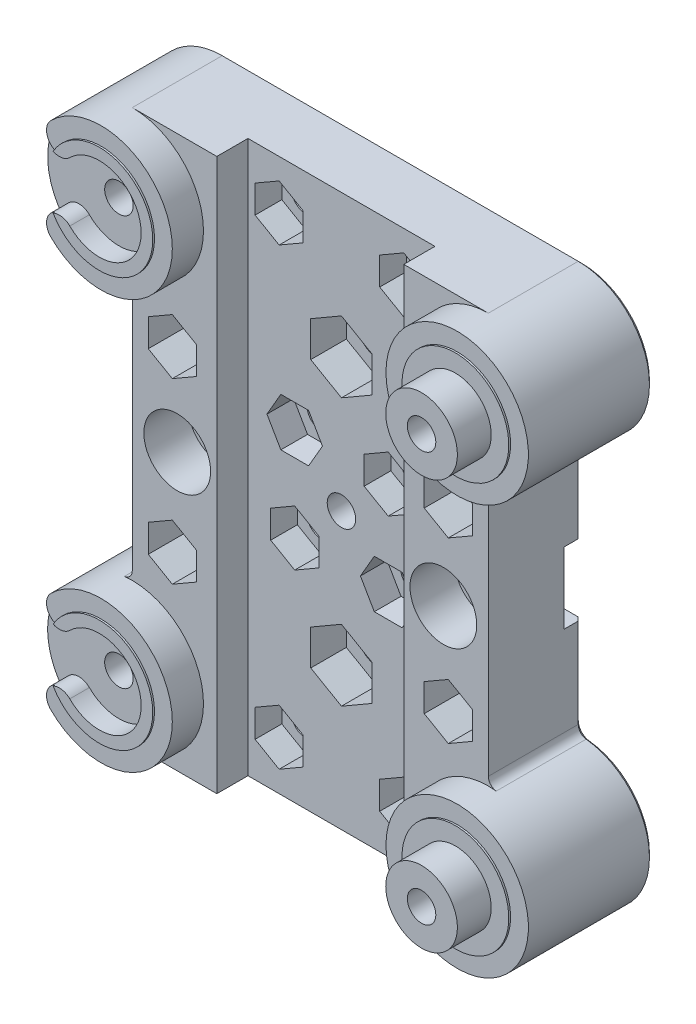
SolidWorks part; units mm, degrees
note: The reader was unsure of these and kept them because the rebuilt part matched: shared geometry of "草图31<3>".
ref_plane "前视基准面" through (0, 0, 0) normal (0, 0, 1) x (1, 0, 0)
ref_plane "上视基准面" through (0, 0, 0) normal (0, 1, 0) x (1, 0, 0)
ref_plane "右视基准面" through (0, 0, 0) normal (1, 0, 0) x (0, 0, -1)
sketch "草图2" plane through (0, 0, 0) normal (0, 0, 1) x (1, 0, 0)
  line L1 (-20, -31) -> (20, -31)
  line L2 (-20, -31) -> (-20, 31)
  line L3 (-20, 31) -> (20, 31)
  line L4 (20, -31) -> (20, 31)
  line L5 (-20, -31) -> (20, 31) construction
  line L6 (-20, 31) -> (20, -31) construction
  point P0 (0, 0)
  dimension "D1" = 40
  dimension "D2" = 62
extrude "凸台-拉伸1" add sketch "草图2" along normal blind 10.5
sketch "草图3" plane through (0, 0, 0) normal (0, 0, -1) x (-1, 0, 0)
  line L2 (20, 31) -> (20, 15)
  arc A0 (20, 15) -> (20, 31) centre (20, 23) ccw
  dimension "D1" = 20
  dimension "D2" = 23
extrude "凸台-拉伸2" add sketch "草图3" against normal blind 10.5
sketch "草图5" plane through (0, 0, 0) normal (0, 0, -1) x (-1, 0, 0)
  line L1 (21.6166, 25.8) -> (18.3834, 25.8)
  line L2 (18.3834, 25.8) -> (16.7668, 23)
  line L3 (16.7668, 23) -> (18.3834, 20.2)
  line L4 (18.3834, 20.2) -> (21.6166, 20.2)
  line L5 (21.6166, 20.2) -> (23.2332, 23)
  line L6 (23.2332, 23) -> (21.6166, 25.8)
  circle A1 centre (20, 23) radius 2.8 construction
  dimension "D1" = 5.6
extrude "切除-拉伸1" cut sketch "草图5" against normal blind 5
sketch "草图29" plane through (0, 0, 10.5) normal (0, 0, 1) x (1, 0, 0)
  circle A0 centre (-20, 23) radius 8
extrude "凸台-拉伸5" add sketch "草图29" along normal blind 3.5
sketch "草图7" plane through (0, 0, 14) normal (0, 0, 1) x (1, 0, 0)
  circle A0 centre (-20, 23) radius 4.025
  dimension "D1" = 8.05
extrude "凸台-拉伸3" add sketch "草图7" along normal blind 9
sketch "草图8" plane through (0, 0, 23) normal (0, 0, 1) x (1, 0, 0)
  circle A0 centre (-20, 23) radius 1.6
  dimension "D1" = 3.2
extrude "切除-拉伸2" cut sketch "草图8" against normal through all
sketch "草图12" plane through (0, 0, 14) normal (0, 0, 1) x (1, 0, 0)
  circle A0 centre (-20, 23) radius 4.025 construction
  circle A1 centre (-20, 23) radius 4.025
  circle A2 centre (-20, 23) radius 6
  dimension "D1" = 12
extrude "凸台-拉伸4" add sketch "草图12" along normal blind 0.2
sketch "草图13" plane through (0, 0, 0) normal (0, 0, -1) x (-1, 0, 0)
  circle A0 centre (-15.5, -10) radius 1.6
  dimension "D1" = 3.2
  dimension "D2" = 10
  dimension "D3" = 15.5
extrude "切除-拉伸5" cut sketch "草图13" against normal through all both and the other way through all
mirror "镜向3" about plane through (0, 0, 0) normal (0, 1, 0) of "切除-拉伸5"
mirror "镜向4" about plane through (0, 0, 0) normal (1, 0, 0) of "切除-拉伸5", "镜向3"
sketch "草图14" plane through (0, 0, 0) normal (0, 0, -1) x (-1, 0, 0)
  line L0 (20, 15) -> (20, -31) construction
  circle A0 centre (14.95, 0) radius 2.05
  dimension "D1" = 4.1
  dimension "D2" = 5.05
extrude "切除-拉伸6" cut sketch "草图14" against normal through all both and the other way through all
sketch "草图15" plane through (0, 0, 0) normal (0, 0, -1) x (-1, 0, 0)
  line L1 (-5.25, -5.25) -> (5.25, -5.25) construction
  line L2 (-5.25, -5.25) -> (-5.25, 5.25) construction
  line L3 (-5.25, 5.25) -> (5.25, 5.25) construction
  line L4 (5.25, -5.25) -> (5.25, 5.25) construction
  line L5 (-5.25, -5.25) -> (5.25, 5.25) construction
  line L6 (-5.25, 5.25) -> (5.25, -5.25) construction
  circle A0 centre (5.25, 5.25) radius 1.6
  point P0 (0, 0)
  dimension "D3" = 3.2
  dimension "D1" = 10.5
  dimension "D2" = 10.5
extrude "切除-拉伸7" cut sketch "草图15" against normal through all both and the other way through all
sketch "草图16" plane through (0, 0, 0) normal (0, 0, -1) x (-1, 0, 0)
  circle A0 centre (0, 0) radius 1.6
  dimension "D1" = 3.2
extrude "切除-拉伸8" cut sketch "草图16" against normal through all both and the other way through all
pattern_circular "阵列(圆周)1" count 4 over 360 about axis through (0, 0, 0) along (0, 0, 1) of "切除-拉伸7"
mirror "镜向5" about plane through (0, 0, 0) normal (1, 0, 0) of "切除-拉伸6"
sketch "草图17" plane through (0, 0, 10.5) normal (0, 0, 1) x (1, 0, 0)
  line L1 (-12.8, 11.5588) -> (-15.5, 13.1177)
  line L2 (-15.5, 13.1177) -> (-18.2, 11.5588)
  line L3 (-18.2, 11.5588) -> (-18.2, 8.4412)
  line L4 (-18.2, 8.4412) -> (-15.5, 6.8823)
  line L5 (-15.5, 6.8823) -> (-12.8, 8.4412)
  line L6 (-12.8, 8.4412) -> (-12.8, 11.5588)
  line L7 (-20, 15) -> (-20, -31) construction
  circle A0 centre (-15.5, 10) radius 2.7 construction
  dimension "D1" = 5.4
extrude "切除-拉伸9" cut sketch "草图17" against normal blind 5 and the other way through all
sketch "草图19" plane through (0, 0, 10.5) normal (0, 0, 1) x (1, 0, 0)
  circle A0 centre (-14.95, 0) radius 3.75
  dimension "D1" = 7.5
extrude "切除-拉伸11" cut sketch "草图19" against normal blind 5
mirror "镜向6" about plane through (0, 0, 0) normal (0, 1, 0) of "凸台-拉伸5", "凸台-拉伸2", "切除-拉伸9", "凸台-拉伸3", "凸台-拉伸4", "切除-拉伸1", "切除-拉伸2"
sketch "草图18" plane through (0, 0, 10.5) normal (0, 0, 1) x (1, 0, 0)
  line L0 (-20, -31) -> (20, -31) construction
  line L1 (-10.5, 31) -> (10.5, 31)
  line L2 (-10.5, 31) -> (-10.5, -31)
  line L3 (-10.5, -31) -> (10.5, -31)
  line L4 (10.5, 31) -> (10.5, -31)
  line L5 (-10.5, 31) -> (10.5, -31) construction
  line L6 (-10.5, -31) -> (10.5, 31) construction
  point P0 (0, 0)
  dimension "D1" = 21
extrude "切除-拉伸10" cut sketch "草图18" against normal offset from surface (3.5 mm away) 7 up to face at (12.9, 0, 0)
mirror "镜向7" about plane through (0, 0, 0) normal (1, 0, 0) of "凸台-拉伸5", "凸台-拉伸3", "切除-拉伸1", "凸台-拉伸2", "切除-拉伸2", "凸台-拉伸4", "切除-拉伸5", "镜向3", "镜向4", "切除-拉伸6", "镜向5", "切除-拉伸9", "切除-拉伸11", "镜向6"
sketch "草图20" plane through (0, 0, 7) normal (0, 0, 1) x (1, 0, 0)
  line L1 (-3.6912, 7.95) -> (-6.8088, 7.95)
  line L2 (-6.8088, 7.95) -> (-8.3677, 5.25)
  line L3 (-8.3677, 5.25) -> (-6.8088, 2.55)
  line L4 (-6.8088, 2.55) -> (-3.6912, 2.55)
  line L5 (-3.6912, 2.55) -> (-2.1323, 5.25)
  line L6 (-2.1323, 5.25) -> (-3.6912, 7.95)
  circle A0 centre (-5.25, 5.25) radius 2.7 construction
  dimension "D1" = 5.4
extrude "切除-拉伸12" cut sketch "草图20" against normal blind 3
pattern_circular "阵列(圆周)2" count 4 over 360 about axis through (0, 0, 0) along (0, 0, 1) of "切除-拉伸12"
sketch "草图21" plane through (0, 0, 7) normal (0, 0, 1) x (1, 0, 0)
  line L0 (10.5, 31) -> (-10.5, 31) construction
  line L1 (-4.3, 27.0588) -> (-7, 28.6177)
  line L2 (-7, 28.6177) -> (-9.7, 27.0588)
  line L3 (-9.7, 27.0588) -> (-9.7, 23.9412)
  line L4 (-9.7, 23.9412) -> (-7, 22.3823)
  line L5 (-7, 22.3823) -> (-4.3, 23.9412)
  line L6 (-4.3, 23.9412) -> (-4.3, 27.0588)
  circle A0 centre (-7, 25.5) radius 2.7 construction
  point P1 (-4.3, 25.5)
  point P9 (-9.7, 25.5)
  dimension "D1" = 5.4
  dimension "D2" = 5.5
  dimension "D3" = 7
extrude "切除-拉伸13" cut sketch "草图21" against normal blind 3
sketch "草图22" plane through (0, 0, 4) normal (0, 0, 1) x (1, 0, 0)
  line L0 (10.5, 31) -> (-10.5, 31) construction
  circle A0 centre (-7, 25.5) radius 1.6
  dimension "D1" = 3.2
  dimension "D2" = 7
  dimension "D3" = 5.5
extrude "切除-拉伸14" cut sketch "草图22" against normal through all
mirror "镜向8" about plane through (0, 0, 0) normal (1, 0, 0) of "切除-拉伸13", "切除-拉伸14"
sketch "草图23" plane through (0, 0, 7) normal (0, 0, 1) x (1, 0, 0)
  line L0 (10.5, 31) -> (-10.5, 31) construction
  circle A0 centre (0, 15) radius 2.1
  dimension "D2" = 4.2
  dimension "D1" = 16
extrude "切除-拉伸15" cut sketch "草图23" against normal through all
sketch "草图24" plane through (0, 0, 7) normal (0, 0, 1) x (1, 0, 0)
  line L1 (0, 18.9837) -> (-3.45, 16.9919)
  line L2 (-3.45, 16.9919) -> (-3.45, 13.0081)
  line L3 (-3.45, 13.0081) -> (0, 11.0163)
  line L4 (0, 11.0163) -> (3.45, 13.0081)
  line L5 (3.45, 13.0081) -> (3.45, 16.9919)
  line L6 (3.45, 16.9919) -> (0, 18.9837)
  circle A0 centre (0, 15) radius 3.45 construction
  dimension "D1" = 6.9
extrude "切除-拉伸16" cut sketch "草图24" against normal blind 4
mirror "镜向9" about plane through (0, 0, 0) normal (0, 1, 0) of "切除-拉伸16", "切除-拉伸15", "镜向8", "切除-拉伸13", "切除-拉伸14"
sketch "草图25" plane through (0, 0, 23) normal (0, 0, 1) x (1, 0, 0)
  circle A1 centre (20, 23) radius 4.025
  circle A2 centre (20, 23) radius 4.025
  circle A3 centre (20, -23) radius 4.025
  circle A4 centre (20, -23) radius 4.025
  dimension "D1" = 0
  dimension "D2" = 0
extrude "切除-拉伸17" cut sketch "草图25" against normal offset from surface (5 mm away) 4 up to face at (26, 23, 14)
sketch "草图26" plane through (0, 0, 23) normal (0, 0, 1) x (1, 0, 0)
  circle A0 centre (-20, 23) radius 4.7
  dimension "D1" = 9.4
extrude "切除-拉伸18" cut sketch "草图26" against normal blind 11
sketch "草图27" plane through (0, 0, 12) normal (0, 0, 1) x (1, 0, 0)
  line L0 (-24.4802, 27.5) -> (-20, 23) construction
  line L1 (-20, 23) -> (-29.8572, 23) construction
  arc A0 (-25.6444, 28.6693) -> (-23.3161, 26.3307) centre (-24.4802, 27.5) ccw
  circle A1 centre (-20, 23) radius 1.6 construction
  arc A2 (-25.6444, 17.3307) -> (-23.3161, 19.6693) centre (-24.4802, 18.5) cw
  arc A4 (-20, 15) -> (-20, 31) centre (-20, 23) ccw construction
  arc A5 (-23.3161, 26.3307) -> (-23.3161, 19.6693) centre (-20, 23) ccw
  arc A6 (-25.6444, 28.6693) -> (-25.6444, 17.3307) centre (-20, 23) ccw
  dimension "D1" = 6.35
  dimension "D2" = 3.3
  dimension "D3" = 4.5
extrude "切除-拉伸19" cut sketch "草图27" along normal through all
mirror "镜向12" about plane through (0, 0, 0) normal (0, 1, 0) of "切除-拉伸19", "切除-拉伸18"
sketch "草图28" plane through (0, 0, 0) normal (0, 1, 0) x (1, 0, 0)
  line L0 (-20, 0) -> (-28, -3)
  line L1 (-20, 0) -> (-28, 0) construction
  line L2 (-28, 0) -> (-28, -12) construction
  line L3 (-28, -3) -> (-28, 0)
  line L4 (-28, 0) -> (-20, 0)
  line L5 (20, 0) -> (-20, 0) construction
  line L6 (-20, -10.5) -> (-20, 0) construction
  dimension "D1" = 3
extrude "切除-拉伸20" [suppressed] cut sketch "草图28" against normal through all both and the other way through all
mirror "镜向13" [suppressed] about plane through (0, 0, 0) normal (1, 0, 0)
fillet "圆角1" radius 1 4 edges at (-20, 15, 5.25) (-20, -15, 5.25) (20, 15, 5.25) (20, -15, 5.25)
sketch "草图31" plane through (0, 0, 5) normal (0, 0, -1) x (-1, 0, 0)
  line L6 (-21.6, 25.8) -> (-21.6, 20.2)
  line L7 (-18.4, 25.8) -> (-18.4, 20.2)
  line L8 (-22.3094, 24.6) -> (-17.6906, 24.6)
  line L9 (-22.3094, 21.4) -> (-17.6906, 21.4)
  line L12 (-21.6166, 25.8) -> (-23.2332, 23)
  line L13 (-23.2332, 23) -> (-21.6166, 20.2)
  line L14 (-21.6166, 20.2) -> (-18.3834, 20.2)
  line L15 (-18.3834, 20.2) -> (-16.7668, 23)
  line L16 (-16.7668, 23) -> (-18.3834, 25.8)
  line L17 (-18.3834, 25.8) -> (-21.6166, 25.8)
  line L18 (-21.6166, 25.8) -> (-23.2332, 23)
  line L19 (-23.2332, 23) -> (-21.6166, 20.2)
  line L20 (-21.6166, 20.2) -> (-18.3834, 20.2)
  line L21 (-18.3834, 20.2) -> (-16.7668, 23)
  line L22 (-16.7668, 23) -> (-18.3834, 25.8)
  line L23 (-18.3834, 25.8) -> (-21.6166, 25.8)
  circle A0 centre (-20, 23) radius 1.6 construction
  line M12 (-21.6166, 25.8) -> (-23.2332, 23)
  line M13 (-23.2332, 23) -> (-21.6166, 20.2)
  line M14 (-21.6166, 20.2) -> (-18.3834, 20.2)
  line M15 (-18.3834, 20.2) -> (-16.7668, 23)
  line M16 (-16.7668, 23) -> (-18.3834, 25.8)
  line M17 (-18.3834, 25.8) -> (-21.6166, 25.8)
  dimension "D1" = 0
extrude "凸台-拉伸6" add sketch "草图31" along normal blind 0.2 contours L6 L8 L7 M17 | L8 L6 M12 M17 | L7 L8 M16 M17 | L9 L7 M14 M15 | L9 L6 L7 M14 | L9 L6 M13 M14
extrude "凸台-拉伸7" add sketch "草图31<3>" along normal blind 0.4 contours L8 L6 M12 M17 | L9 L6 L8 M13 M12 | L9 L6 M13 M14 | L7 L8 M16 M17 | L7 L9 L8 M15 M16 | L9 L7 M14 M15
sketch "草图31<3>" plane through (0, 0, 5) normal (0, 0, -1) x (-1, 0, 0) same geometry as "草图31"
mirror "镜向14" about plane through (0, 0, 0) normal (0, 1, 0) of "凸台-拉伸6", "凸台-拉伸7"
mirror "镜向15" about plane through (0, 0, 0) normal (1, 0, 0) of "镜向14", "凸台-拉伸6", "凸台-拉伸7"
sketch "草图32" plane through (0, 0, 0) normal (0, 1, 0) x (1, 0, 0)
  line L0 (18, 0) -> (20, -2)
  line L1 (20, 0) -> (-20, 0) construction
  line L2 (20, -10.5) -> (20, 0) construction
  line L5 (18, 0) -> (20, 0)
  line L6 (20, 0) -> (20, -2)
  dimension "D1" = 2
  dimension "D2" = 2
extrude "切除-拉伸22" cut sketch "草图32" against normal mid plane 8
mirror "镜向16" about plane through (0, 0, 0) normal (1, 0, 0) of "切除-拉伸22"
chamfer "倒角1" distance 0.4 angle 45 14 edges at (20, 9.0279, 0) (-20, -9.0279, 0) (0, -31, 0) (0, 31, 0) (-27.9876, -23.4451, 0) (-20, 9.0279, 0) (-27.9876, 23.4451, 0) (20, -9.0279, 0) (27.9876, -23.4451, 0) (27.9876, 23.4451, 0) (-20.2546, -14.7224, 0) (-20.2546, 14.7224, 0) (20.2546, -14.7224, 0) (20.2546, 14.7224, 0)
chamfer "倒角2" distance 0.4 angle 45 17 edges at (5.4, 25.5, 0) (-5.4, 25.5, 0) (13.9, 10, 0) (2.1, 15, 0) (-17.1, 10, 0) (-6.85, 5.25, 0) (3.65, 5.25, 0) (12.9, 0, 0) (-1.6, 0, 0) (-17, 0, 0) (-6.85, -5.25, 0) (3.65, -5.25, 0) (13.9, -10, 0) (-17.1, -10, 0) (2.1, -15, 0) (5.4, -25.5, 0) (-5.4, -25.5, 0)
chamfer "倒角3" distance 0.4 angle 45 24 edges at (20, 20.2, 0) (17.5751, 21.6, 0) (17.5751, 24.4, 0) (20, 25.8, 0) (22.4249, 24.4, 0) (22.4249, 21.6, 0) (20, -25.8, 0) (17.5751, -24.4, 0) (17.5751, -21.6, 0) (20, -20.2, 0) (22.4249, -21.6, 0) (22.4249, -24.4, 0) (-20, -20.2, 0) (-17.5751, -21.6, 0) (-17.5751, -24.4, 0) (-20, -25.8, 0) (-22.4249, -24.4, 0) (-22.4249, -21.6, 0) (-20, 25.8, 0) (-17.5751, 24.4, 0) (-17.5751, 21.6, 0) (-20, 20.2, 0) (-22.4249, 21.6, 0) (-22.4249, 24.4, 0)
sketch "草图33" plane through (0, 0, 0) normal (0, 0, -1) x (-1, 0, 0)
  line L0 (0, 32.6549) -> (0, -34.2846)
  line L1 (-20, 31) -> (20, 31) construction
  line L2 (-3.25, 29) -> (3.25, 29)
  line L3 (-3.25, 29) -> (-3.25, 30)
  line L4 (-3.25, 30) -> (3.25, 30)
  line L5 (3.25, 29) -> (3.25, 30)
  line L6 (-3.25, 29) -> (3.25, 30) construction
  line L7 (-3.25, 30) -> (3.25, 29) construction
  point P3 (0, 29.5)
  dimension "D1" = 1
  dimension "D2" = 6.5
  dimension "D3" = 1
extrude "切除-拉伸23" cut sketch "草图33" against normal blind 1 contours L4 L3 L2 L0 | L2 L5 L4 L0
pattern_linear "阵列(线性)1" count 5 spacing 2 along (0, -1, 0) of "切除-拉伸23"
mirror "镜向17" about plane through (0, 0, 0) normal (0, 1, 0) of "切除-拉伸23", "阵列(线性)1"
